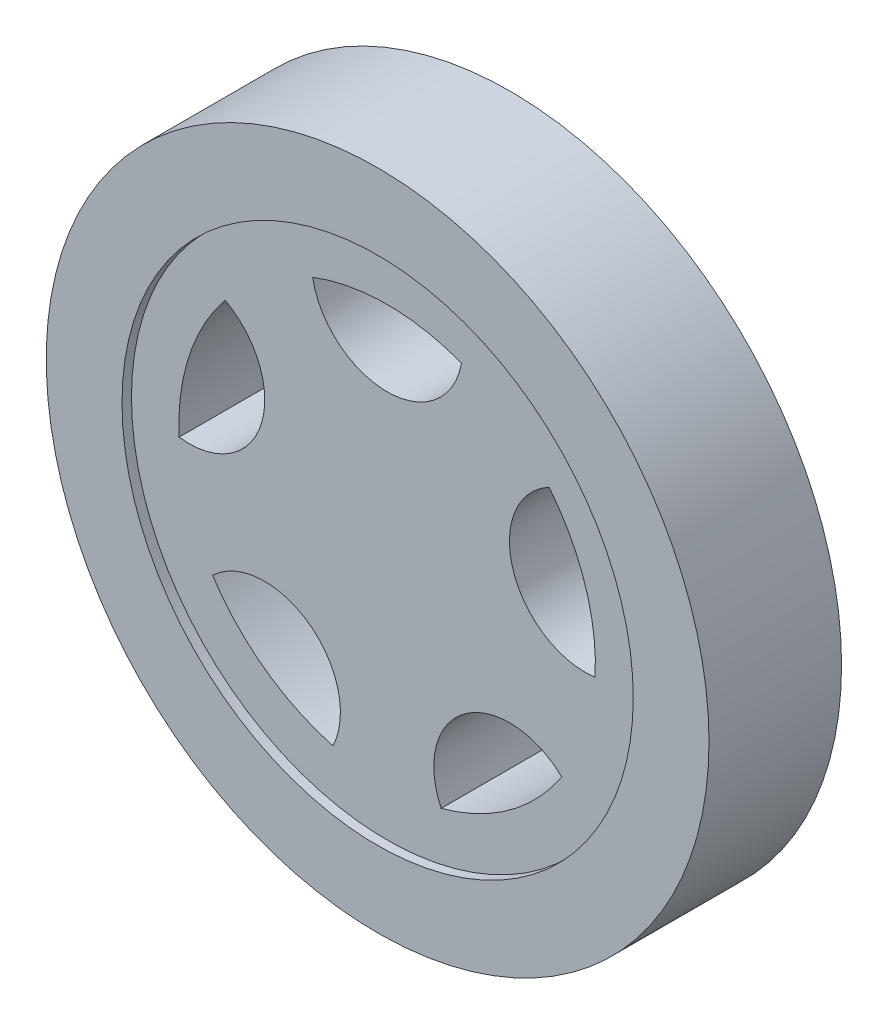
SolidWorks part; units mm, degrees
ref_plane "정면" through (0, 0, 0) normal (0, 0, 1) x (1, 0, 0)
ref_plane "윗면" through (0, 0, 0) normal (0, 1, 0) x (1, 0, 0)
ref_plane "우측면" through (0, 0, 0) normal (1, 0, 0) x (0, 0, -1)
sketch "스케치1" plane through (0, 0, 0) normal (0, 0, 1) x (1, 0, 0)
  circle A0 centre (0, 0) radius 175
  dimension "D1" = 350
extrude "보스-돌출1" add sketch "스케치1" along normal blind 35 and the other way blind 35
sketch "스케치2" plane through (0, 0, 35) normal (0, 0, 1) x (1, 0, 0)
  arc A0 (39.3333, 102.7273) -> (-39.3333, 102.7273) centre (0, 0) ccw
  arc A1 (-39.3333, 102.7273) -> (39.3333, 102.7273) centre (0, 110) ccw
  arc A2 (-85.5448, 69.1527) -> (-109.8541, -5.6637) centre (0, 0) ccw
  arc A3 (-109.8541, -5.6637) -> (-85.5448, 69.1527) centre (-104.6162, 33.9919) ccw
  arc A4 (-92.2029, -59.9886) -> (-28.5603, -106.2276) centre (0, 0) ccw
  arc A5 (-28.5603, -106.2276) -> (-92.2029, -59.9886) centre (-64.6564, -88.9919) ccw
  arc A6 (28.5603, -106.2276) -> (92.2029, -59.9886) centre (0, 0) ccw
  arc A7 (92.2029, -59.9886) -> (28.5603, -106.2276) centre (64.6564, -88.9919) ccw
  arc A8 (109.8541, -5.6637) -> (85.5448, 69.1527) centre (0, 0) ccw
  arc A9 (85.5448, 69.1527) -> (109.8541, -5.6637) centre (104.6162, 33.9919) ccw
  point P19 (0, 0)
  dimension "D1" = 220
  dimension "D2" = 40
  dimension "D3" = 5
extrude "컷-돌출2" cut sketch "스케치2" against normal through all
sketch "스케치3" plane through (0, 0, 35) normal (0, 0, 1) x (1, 0, 0)
  circle A0 centre (0, 0) radius 135
  dimension "D1" = 270
extrude "컷-돌출3" cut sketch "스케치3" against normal blind 5
mirror "대칭 복사1" about plane through (0, 0, 0) normal (0, 0, 1) of "컷-돌출3"
sketch "스케치4" plane through (0, 0, -30) normal (0, 0, -1) x (-1, 0, 0)
  circle A0 centre (0, 0) radius 10
  dimension "D1" = 20
extrude "컷-돌출4" cut sketch "스케치4" against normal blind 30
